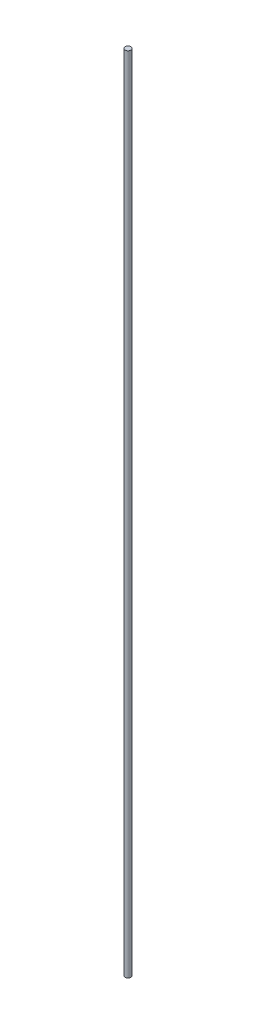
SolidWorks part; units mm, degrees
ref_plane "Front Plane" through (0, 0, 0) normal (0, 0, 1) x (1, 0, 0)
ref_plane "Top Plane" through (0, 0, 0) normal (0, 1, 0) x (1, 0, 0)
ref_plane "Right Plane" through (0, 0, 0) normal (1, 0, 0) x (0, 0, -1)
sketch "Sketch1" plane through (0, 0, 0) normal (0, 1, 0) x (1, 0, 0)
  circle A0 centre (0, 0) radius 5.5
  dimension "D1" = 11
extrude "Boss-Extrude1" add sketch "Sketch1" along normal blind 1500
